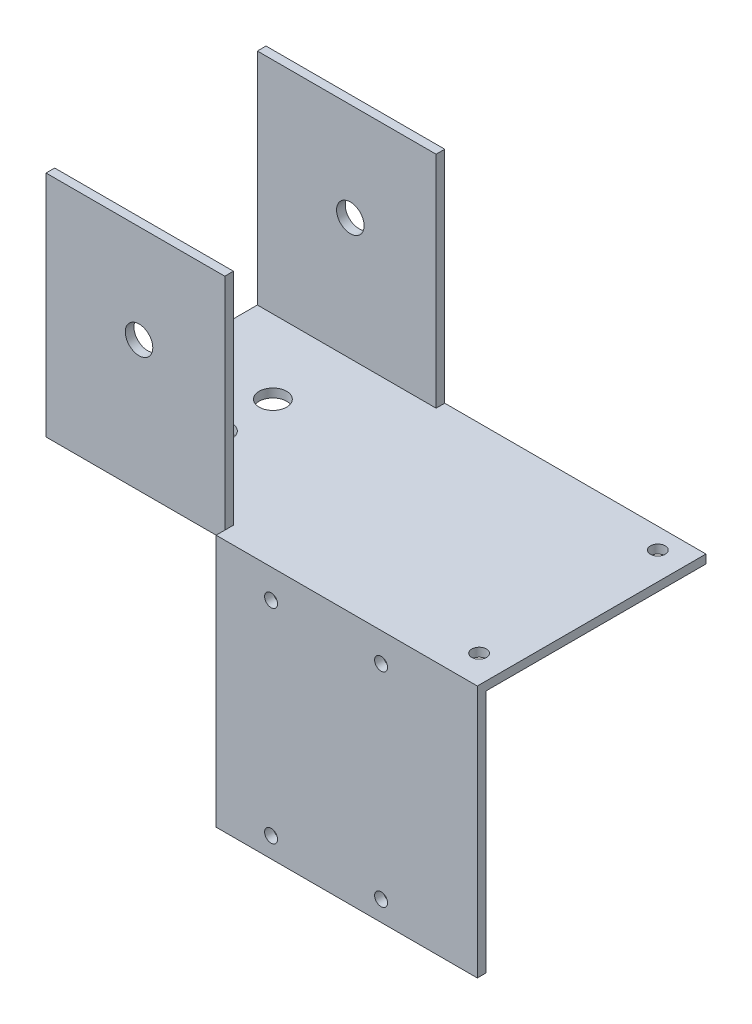
SolidWorks part; units mm, degrees
material "Galvanized Steel"
ref_plane "Front Plane" through (0, 0, 0) normal (0, 0, 1) x (1, 0, 0)
ref_plane "Top Plane" through (0, 0, 0) normal (0, 1, 0) x (1, 0, 0)
ref_plane "Right Plane" through (0, 0, 0) normal (1, 0, 0) x (0, 0, -1)
sketch "Sketch1" plane through (0, 0, 0) normal (0, 0, 1) x (1, 0, 0)
  line L0 (38.1, 51.75) -> (12.7, 51.75) construction
  line L1 (0, 58.4) -> (60.325, 58.4)
  line L2 (0, 58.4) -> (0, 0)
  line L3 (0, 0) -> (60.325, 0)
  line L4 (60.325, 58.4) -> (60.325, 0)
  line L6 (12.7, 51.75) -> (12.7, 4.65) construction
  line L8 (12.7, 4.65) -> (38.1, 4.65) construction
  line L9 (38.1, 51.75) -> (38.1, 4.65) construction
  circle A4 centre (12.7, 51.75) radius 1.5
  circle A5 centre (38.1, 51.75) radius 1.5
  circle A6 centre (12.7, 4.65) radius 1.5
  circle A7 centre (38.1, 4.65) radius 1.5
  dimension "D3" = 3
  dimension "D1" = 58.4
  dimension "D4" = 47.1
  dimension "D5" = 60.325
  dimension "D6" = 4.65
  dimension "D7" = 25.4
  dimension "D9" = 12.7
extrude "Boss-Extrude1" add sketch "Sketch1" against normal blind 2
sketch "Sketch2" plane through (0, 0, -2) normal (0, 0, -1) x (-1, 0, 0)
  line L0 (0, 56.4) -> (41.275, 56.4)
  line L1 (0, 58.4) -> (0, 0) construction
  line L2 (0, 56.4) -> (-60.325, 56.4)
  line L3 (-60.325, 56.4) -> (-60.325, 58.4)
  line L5 (-60.325, 58.4) -> (0, 58.4)
  line L6 (41.275, 56.4) -> (41.275, 58.4)
  line L7 (41.275, 58.4) -> (0, 58.4)
  dimension "D1" = 60.325
  dimension "D2" = 41.275
  dimension "D3" = 2
extrude "Boss-Extrude2" add sketch "Sketch2" along normal blind 50.8
sketch "Sketch3" plane through (0, 58.4, 0) normal (0, 1, 0) x (1, 0, 0)
  line L0 (53.975, 48.0375) -> (53.975, 6.7625) construction
  line L1 (-41.275, 52.8) -> (60.325, 52.8) construction
  line L2 (60.325, 52.8) -> (60.325, 0) construction
  line L3 (-20.6375, 33.75) -> (-20.6375, 21.05) construction
  line L4 (-41.275, 52.8) -> (-41.275, 2) construction
  circle A0 centre (53.975, 48.0375) radius 1.7
  circle A1 centre (53.975, 6.7625) radius 1.7
  circle A2 centre (-20.6375, 33.75) radius 3.175
  circle A3 centre (-20.6375, 21.05) radius 3.175
  point P10 (-20.6375, 27.4)
  point P13 (-41.275, 27.4)
  dimension "D1" = 3.4
  dimension "D2" = 41.275
  dimension "D6" = 6.35
  dimension "D7" = 6.35
  dimension "D3" = 4.7625
  dimension "D4" = 6.35
  dimension "D5" = 12.7
  dimension "D8" = 20.6375
extrude "Cut-Extrude1" cut sketch "Sketch3" against normal through all
sketch "Sketch4" plane through (0, 58.4, 0) normal (0, 1, 0) x (1, 0, 0)
  line L1 (-41.275, 2) -> (0, 2)
  line L2 (-41.275, 2) -> (-41.275, 4)
  line L3 (-41.275, 4) -> (0, 4)
  line L4 (0, 2) -> (0, 4)
  line L5 (-41.275, 52.8) -> (0, 52.8)
  line L6 (-41.275, 52.8) -> (-41.275, 50.8)
  line L7 (-41.275, 50.8) -> (0, 50.8)
  line L8 (0, 52.8) -> (0, 50.8)
  point P10 (20.9088, 4)
  point P11 (0, 0)
  dimension "D1" = 2
  dimension "D2" = 2
extrude "Boss-Extrude3" add sketch "Sketch4" along normal blind 50.8
sketch "Sketch5" plane through (0, 0, -2) normal (0, 0, 1) x (1, 0, 0)
  line L0 (60.325, 58.4) -> (0, 58.4) construction
  line L1 (-41.275, 56.4) -> (-41.275, 109.2) construction
  circle A0 centre (-19.8, 86.568) radius 3.175
  dimension "D1" = 6.35
  dimension "D2" = 28.168
  dimension "D3" = 21.475
extrude "Cut-Extrude2" cut sketch "Sketch5" against normal through all
